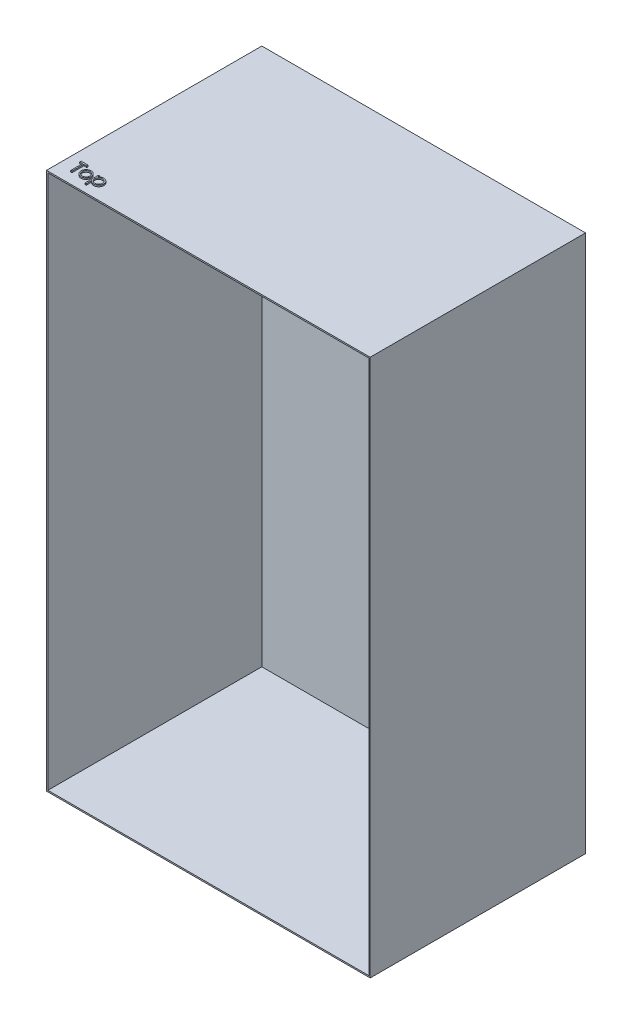
SolidWorks part; units mm, degrees
ref_plane "Front Plane" through (0, 0, 0) normal (0, 0, 1) x (1, 0, 0)
ref_plane "Top Plane" through (0, 0, 0) normal (0, 1, 0) x (1, 0, 0)
ref_plane "Right Plane" through (0, 0, 0) normal (1, 0, 0) x (0, 0, -1)
sketch "Sketch1" plane through (0, 0, 0) normal (0, 0, 1) x (1, 0, 0)
  line L0 (-230.6, 383) -> (230.6, 383)
  line L1 (-228.6, 381) -> (228.6, 381)
  line L2 (-228.6, 381) -> (-228.6, -381)
  line L3 (-228.6, -381) -> (228.6, -381)
  line L4 (228.6, 381) -> (228.6, -381)
  line L5 (230.6, 383) -> (230.6, -383)
  line L6 (-230.6, -383) -> (230.6, -383)
  line L7 (-230.6, 383) -> (-230.6, -383)
  dimension "D1" = 457.2
  dimension "D2" = 762
  dimension "D3" = 228.6
  dimension "D4" = 381
  dimension "D5" = 2
extrude "Boss-Extrude1" add sketch "Sketch1" against normal blind 2 contours L0 L5 L6 L7
extrude "Boss-Extrude4" add sketch "Sketch1<6>" along normal blind 304.8
sketch "Sketch1<6>" plane through (0, 0, 0) normal (0, 0, 1) x (1, 0, 0) same geometry as "Sketch1"
sketch "Sketch4" plane through (0, 383, 0) normal (0, 1, 0) x (1, 0, 0)
  line L0 (-230.6, 2) -> (-230.6, -304.8) construction
  line L1 (230.6, -304.8) -> (-230.6, -304.8) construction
  text T0 "Top" font "Century Gothic" height in points 72
  dimension "D1" = 15
  dimension "D2" = 15
extrude "Boss-Extrude5" add sketch "Sketch4" along normal blind 2
equation "\"D4@Sketch1\"=\"D2@Sketch1\"/2"
equation "\"D3@Sketch1\"=\"D1@Sketch1\"/2"
